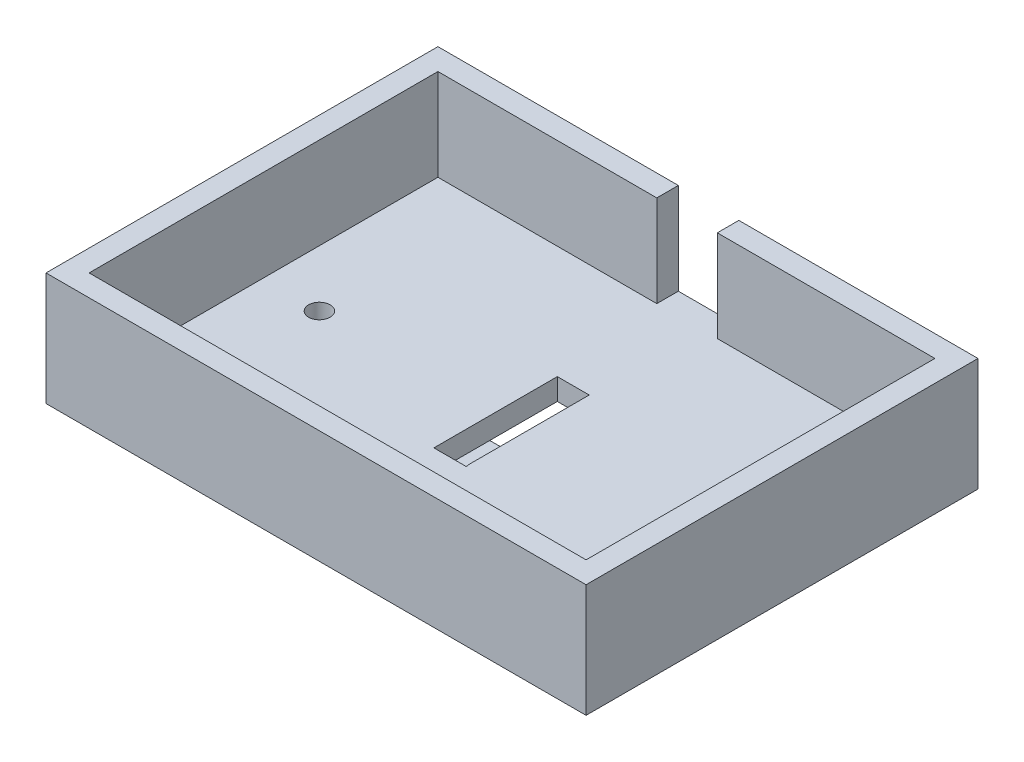
SolidWorks part; units mm, degrees
ref_plane "Front Plane" through (0, 0, 0) normal (0, 0, 1) x (1, 0, 0)
ref_plane "Top Plane" through (0, 0, 0) normal (0, 1, 0) x (1, 0, 0)
ref_plane "Right Plane" through (0, 0, 0) normal (1, 0, 0) x (0, 0, -1)
sketch "Sketch1" plane through (0, 0, 0) normal (0, 1, 0) x (1, 0, 0)
  line L0 (-41.9141, 29.9534) -> (-41.9141, 25.9534)
  line L1 (-41.9141, 25.9534) -> (50.3359, 25.9534)
  line L2 (-41.9141, 25.9534) -> (-41.9141, -38.7966)
  line L3 (-41.9141, -38.7966) -> (50.3359, -38.7966)
  line L4 (50.3359, 25.9534) -> (50.3359, -38.7966)
  line L5 (-45.9141, 29.9534) -> (54.3359, 29.9534)
  line L6 (-45.9141, 29.9534) -> (-45.9141, -42.7966)
  line L7 (-45.9141, -42.7966) -> (54.3359, -42.7966)
  line L8 (54.3359, 29.9534) -> (54.3359, -42.7966)
  line L9 (-45.9141, 25.9534) -> (-41.9141, 25.9534)
  line L10 (54.3359, -38.7966) -> (50.3359, -38.7966)
  line L11 (50.3359, -42.7966) -> (50.3359, -38.7966)
  dimension "D1" = 92.25
  dimension "D2" = 64.75
  dimension "D3" = 4
  dimension "D4" = 4
  dimension "D5" = 4
  dimension "D6" = 4
extrude "Boss-Extrude1" add sketch "Sketch1" along normal blind 4 contours L10 L8 L5 L0 L1 L4 | L6 L9 L0 L5 | L7 L11 L3 L2 L9 L6 | L11 L7 L8 L10 | L4 L1 L2 L3 region at (6.2109, 0, -28.7706) region at (-43.9141, 0, -27.9534) region at (4.2109, 0, 6.4216) region at (-43.097, 0, 6.4216) region at (52.3359, 0, 40.7966)
extrude "Boss-Extrude2" add sketch "Sketch1<3>" along normal blind 21 contours L10 L8 L5 L0 L1 L4 | L6 L9 L0 L5 | L7 L11 L3 L2 L9 L6 | L11 L7 L8 L10 region at (6.2109, 0, -28.7706) region at (-43.9141, 0, -27.9534) region at (-43.097, 0, 6.4216) region at (52.3359, 0, 40.7966)
sketch "Sketch1<3>" plane through (0, 0, 0) normal (0, 1, 0) x (1, 0, 0) same geometry as "Sketch1"
sketch "Sketch2" plane through (0, 0, 0) normal (0, -1, 0) x (1, 0, 0)
  line L0 (-45.9141, 42.7966) -> (54.3359, -29.9534)
  line L1 (4.2109, 6.4216) -> (4.2109, 17.9216)
  line L2 (4.2109, 17.9216) -> (1.2109, 17.9216)
  line L3 (1.2109, 17.9216) -> (1.2109, -4.9531)
  line L4 (1.2109, -4.9531) -> (4.813, -4.9531)
  line L5 (4.813, -4.9531) -> (7.2109, 17.9216)
  line L6 (7.2109, 17.9216) -> (4.2109, 17.9216)
  line L7 (7.2109, 17.9216) -> (7.2109, -4.9531)
  line L8 (-45.9141, -29.9534) -> (-45.9141, 42.7966) construction
  line L9 (-45.9141, 6.4216) -> (-31.4147, 6.5466)
  line L10 (7.2109, -4.9531) -> (1.2109, -4.9531)
  circle A0 centre (-31.4147, 6.5466) radius 2
  dimension "D1" = 3
  dimension "D2" = 23
  dimension "D3" = 11.5
  dimension "D4" = 14.5
extrude "Cut-Extrude1" cut sketch "Sketch2" against normal blind 21 contours L5 L6 L1 L0 | L2 L3 L0 L1 | L4 L5 L0 L3 region at (2.7631, 0, 12.6969) region at (3.2069, 0, 1.2962) region at (5.4321, 0, 12.4021)
extrude "Cut-Extrude3" cut sketch "Sketch2<4>" against normal blind 21 contours A0 region at (-31.4063, 0, 4.6032)
sketch "Sketch2<4>" plane through (0, 0, 0) normal (0, -1, 0) x (1, 0, 0) same geometry as "Sketch2"
sketch "Sketch5" plane through (0, 0, 0) normal (0, -1, 0) x (-1, 0, 0)
  line L0 (-7.2109, -17.9216) -> (-7.2109, -21.9216)
  line L1 (-7.2109, -21.9216) -> (-8.7109, -21.9216)
  line L2 (-1.2109, -17.9216) -> (-1.2109, -22.0466)
  line L3 (-1.2109, -22.0466) -> (0.2891, -22.0466)
  line L5 (-8.7109, -21.9216) -> (-12.7109, -21.9216)
  line L6 (-8.7109, -21.9216) -> (-8.7109, -25.9216)
  line L7 (-8.7109, -25.9216) -> (-12.7109, -25.9216)
  line L8 (-12.7109, -21.9216) -> (-12.7109, -25.9216)
  line L9 (0.2891, -22.0466) -> (4.2891, -22.0466)
  line L10 (0.2891, -22.0466) -> (0.2891, -26.0466)
  line L11 (0.2891, -26.0466) -> (4.2891, -26.0466)
  line L12 (4.2891, -22.0466) -> (4.2891, -26.0466)
  point P15 (2.2891, -22.0466)
  dimension "D1" = 4
  dimension "D2" = 1.5
  dimension "D3" = 4
  dimension "D4" = 4
  dimension "D5" = 4
  dimension "D6" = 4
extrude "Boss-Extrude3" add sketch "Sketch5" along normal blind 9.5 contours L5 L8 L7 L6 | L12 L9 L10 L11 region at (10.7109, 0, 23.9216) region at (-2.2891, 0, 24.0466)
sketch "Sketch7" plane through (0, 0, 22.0466) normal (0, 0, -1) x (-1, 0, 0)
  line L0 (0.2891, -9.5) -> (0.2891, 0) construction
  line L1 (4.2891, -9.5) -> (0.2891, -9.5)
  line L2 (4.2891, -9.5) -> (4.2891, -5.5)
  line L3 (4.2891, -5.5) -> (0.2891, -5.5)
  line L4 (0.2891, -9.5) -> (0.2891, -5.5)
  line L5 (-8.7109, -9.5) -> (-8.7109, 0) construction
  line L6 (-12.7109, -9.5) -> (-8.7109, -9.5)
  line L7 (-12.7109, -9.5) -> (-12.7109, -5.5)
  line L8 (-12.7109, -5.5) -> (-8.7109, -5.5)
  line L9 (-8.7109, -9.5) -> (-8.7109, -5.5)
  dimension "D1" = 4
extrude "Boss-Extrude4" add sketch "Sketch7" along normal blind 20
sketch "Sketch8" plane through (0, 0, -29.9534) normal (0, 0, -1) x (-1, 0, 0)
  line L0 (-54.3359, 21) -> (45.9141, 0)
  line L1 (-4.4436, 10.5488) -> (-4.4436, 21)
  line L2 (45.9141, 21) -> (-54.3359, 21) construction
  line L3 (-4.4436, 21) -> (-9.9436, 21)
  line L4 (-9.9436, 21) -> (-9.9436, 4)
  line L5 (-9.9436, 4) -> (-9.9436, 0)
  line L6 (45.9141, 0) -> (-54.3359, 0) construction
  line L7 (-9.9436, 0) -> (-4.4384, 0)
  line L8 (-4.4384, 0) -> (1.2891, 0)
  line L9 (1.2891, 0) -> (1.2891, 21)
  line L10 (1.2891, 21) -> (-4.2109, 21)
  line L11 (-9.9436, 4) -> (1.2891, 4)
  line M5 (45.9141, 21) -> (-54.3359, 21)
  dimension "D1" = 5.5
  dimension "D2" = 4
extrude "Cut-Extrude4" cut sketch "Sketch8" against normal blind 10 contours L0 L9 L1 M5 | L4 L0 L1 M5 | L4 L11 L9 L0 region at (7.1401, 16.0568, -29.9534) region at (4.6648, 7.2975, -29.9534) region at (1.5253, 15.4687, -29.9534)
sketch "Sketch10" plane through (0, 0, 0) normal (0, -1, 0) x (1, 0, 0)
  line L1 (1.2109, 17.9216) -> (7.1292, 17.9216)
  line L2 (1.2109, 17.9216) -> (1.2109, -4.9913)
  line L3 (1.2109, -4.9913) -> (7.1292, -4.9913)
  line L4 (7.1292, 17.9216) -> (7.1292, -4.9913)
extrude "Cut-Extrude5" cut sketch "Sketch10" against normal blind 10
